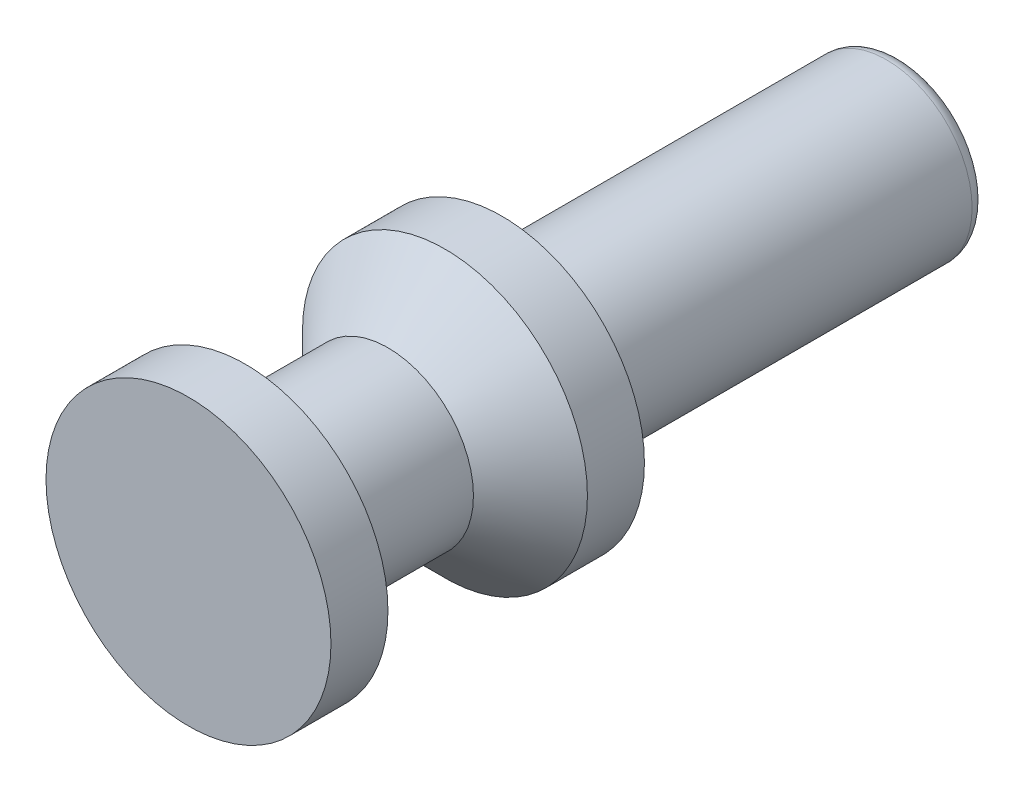
SolidWorks part; units mm, degrees
ref_plane "Front Plane" through (0, 0, 0) normal (0, 0, 1) x (1, 0, 0)
ref_plane "Top Plane" through (0, 0, 0) normal (0, 1, 0) x (1, 0, 0)
ref_plane "Right Plane" through (0, 0, 0) normal (1, 0, 0) x (0, 0, -1)
sketch "Sketch1" plane through (0, 0, 0) normal (0, 0, 1) x (1, 0, 0)
  circle A0 centre (0, 0) radius 1.5
  dimension "D1" = 3
extrude "Boss-Extrude1" add sketch "Sketch1" along normal blind 12.5
sketch "Sketch2" plane through (0, 0, 12.5) normal (0, 0, 1) x (1, 0, 0)
  circle A0 centre (0, 0) radius 2.5
  dimension "D1" = 5
extrude "Boss-Extrude2" add sketch "Sketch2" against normal blind 1
fillet "Fillet1" radius 0.25 1 edges at (1.5, 0, 0)
sketch "Sketch4" plane through (0, 0, 12.5) normal (0, 0, 1) x (1, 0, 0)
  circle A0 centre (0, 0) radius 2.5
extrude "Boss-Extrude4" add sketch "Sketch4" against normal blind 1 from offset 4.5 offset against normal yes
chamfer "Chamfer2" distance 1 angle 45 1 edges at (1.5, 0, 8)
